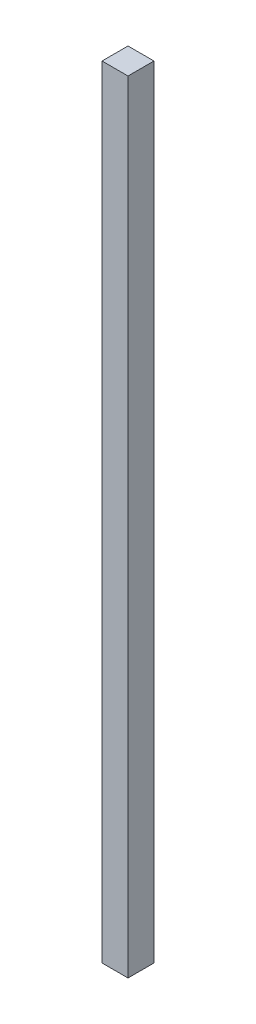
SolidWorks part; units mm, degrees
ref_plane "Front Plane" through (0, 0, 0) normal (0, 0, 1) x (1, 0, 0)
ref_plane "Top Plane" through (0, 0, 0) normal (0, 1, 0) x (1, 0, 0)
ref_plane "Right Plane" through (0, 0, 0) normal (1, 0, 0) x (0, 0, -1)
sketch "Sketch1" plane through (0, 0, 0) normal (0, 1, 0) x (1, 0, 0)
  line L7 (-1.9, -1.9) -> (1.9, -1.9)
  line L8 (-1.9, -1.9) -> (-1.9, 1.9)
  line L9 (-1.9, 1.9) -> (1.9, 1.9)
  line L10 (1.9, -1.9) -> (1.9, 1.9)
  line L11 (-1.9, -1.9) -> (1.9, 1.9) construction
  line L12 (-1.9, 1.9) -> (1.9, -1.9) construction
  dimension "D2" = 3.8
  dimension "D3" = 3.8
extrude "Boss-Extrude1" add sketch "Sketch1" along normal blind 114.3
